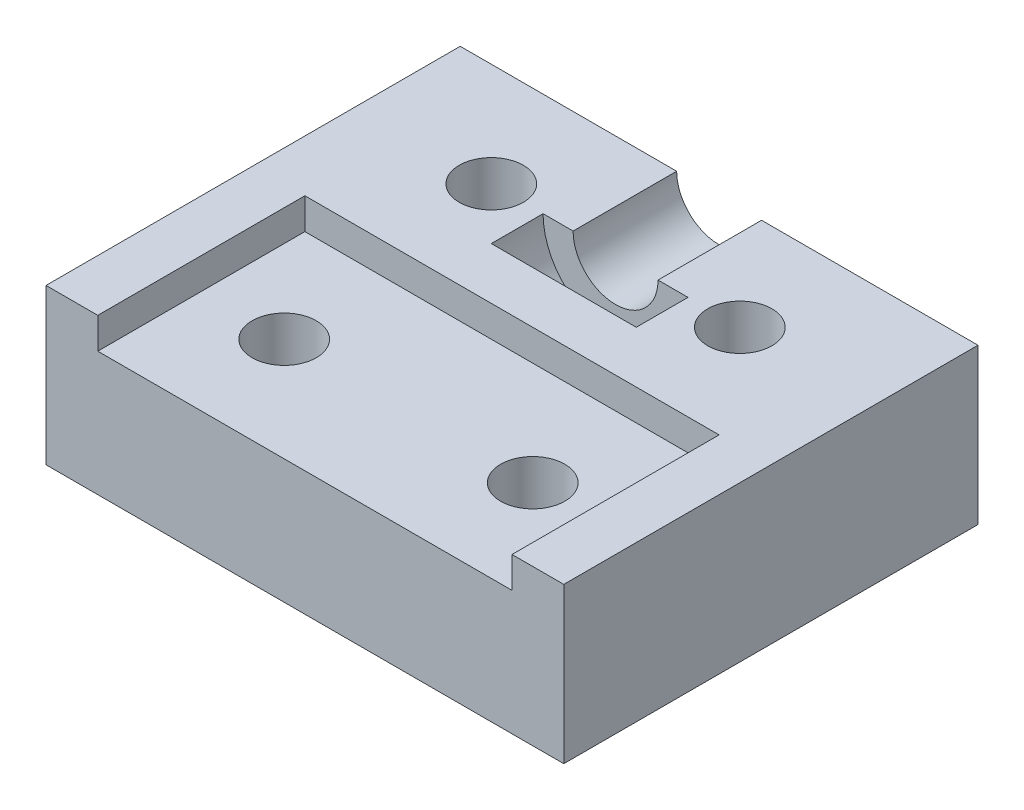
SolidWorks part; units mm, degrees
ref_plane "Front Plane" through (0, 0, 0) normal (0, 0, 1) x (1, 0, 0)
ref_plane "Top Plane" through (0, 0, 0) normal (0, 1, 0) x (1, 0, 0)
ref_plane "Right Plane" through (0, 0, 0) normal (1, 0, 0) x (0, 0, -1)
sketch "Sketch2" plane through (0, 0, 0) normal (0, 1, 0) x (1, 0, 0)
  line L1 (12.5, 10) -> (-12.5, 10)
  line L2 (12.5, 10) -> (12.5, -10)
  line L3 (12.5, -10) -> (-12.5, -10)
  line L4 (-12.5, 10) -> (-12.5, -10)
  line L5 (12.5, 10) -> (-12.5, -10) construction
  line L6 (12.5, -10) -> (-12.5, 10) construction
  point P0 (0, 0)
  dimension "D1" = 20
  dimension "D2" = 25
extrude "Boss-Extrude1" add sketch "Sketch2" against normal blind 7.5
sketch "Sketch3" plane through (0, 0, 10) normal (0, 0, 1) x (1, 0, 0)
  line L1 (10, 1.5) -> (-10, 1.5)
  line L2 (10, 1.5) -> (10, -1.5)
  line L3 (10, -1.5) -> (-10, -1.5)
  line L4 (-10, 1.5) -> (-10, -1.5)
  line L5 (10, 1.5) -> (-10, -1.5) construction
  line L6 (10, -1.5) -> (-10, 1.5) construction
  point P0 (0, 0)
  dimension "D1" = 3
  dimension "D2" = 20
extrude "Cut-Extrude1" cut sketch "Sketch3" against normal blind 10
ref_plane "Plane1" through (0, 0, -5) normal (0, 0, 1) x (1, 0, 0)
sketch "Sketch4" plane through (0, 0, -5) normal (0, 0, 1) x (1, 0, 0)
  circle A0 centre (0, 0) radius 3.5
  dimension "D1" = 7
extrude "Cut-Extrude2" cut sketch "Sketch4" along normal blind 2.5
sketch "Sketch5" plane through (0, 0, -5) normal (0, 0, 1) x (1, 0, 0)
  circle A0 centre (0, 0) radius 2.05
  dimension "D1" = 4.1
extrude "Cut-Extrude3" cut sketch "Sketch5" against normal through all contours A0
sketch "Sketch6" plane through (0, -1.5, 0) normal (0, 1, 0) x (1, 0, 0)
  line L0 (0, 10) -> (0, -10) construction
  line L1 (2.05, 10) -> (-2.05, 10) construction
  line L2 (-10, -10) -> (10, -10) construction
  line L3 (-12.5, -5) -> (12.5, -5) construction
  line L4 (-12.5, 10) -> (-12.5, -10) construction
  line L5 (12.5, -10) -> (12.5, 10) construction
  point P12 (-6, -5)
  point P13 (6, -5)
  dimension "D1" = 5
  dimension "D2" = 12
hole_wizard "Ø3.1 (3.1) Diameter Hole1" positions "Sketch7" profile "Sketch8" hole size "Ø3.1" standard "ISO" end condition through all
sketch "Sketch7" plane through (0, -1.5, 0) normal (0, 1, 0) x (1, 0, 0)
  point P0 (-6, -5)
  point P3 (6, -5)
sketch "Sketch8" plane through (-6, -1.5, 5) normal (1, 0, 0) x (0, 0, 1)
  line L0 (0, 0) -> (0, 6)
  line L1 (0, 6) -> (1.55, 6)
  line L2 (1.55, 6) -> (1.55, 0)
  line L5 (1.55, 0) -> (0, 0)
  line L11 (0, -6.35) -> (0, 107.95) construction
  dimension "Thru Hole Dia." = 3.1
  dimension "Thru Hole Depth" = 6
sketch "Sketch9" plane through (0, 0, 0) normal (0, 1, 0) x (1, 0, 0)
  line L0 (-12.5, 5) -> (12.5, 5) construction
  line L1 (-12.5, 10) -> (-12.5, -10) construction
  line L2 (12.5, -10) -> (12.5, 10) construction
  line L3 (0, 10) -> (0, -10) construction
  line L4 (2.05, 10) -> (-2.05, 10) construction
  line L5 (-10, -10) -> (10, -10) construction
  line L6 (-2.05, 10) -> (-12.5, 10) construction
  point P14 (-6, 5)
  point P15 (6, 5)
  dimension "D1" = 5
  dimension "D2" = 12
hole_wizard "Ø3.1 (3.1) Diameter Hole2" positions "Sketch10" profile "Sketch11" hole size "Ø3.1" standard "ISO" end condition through all
sketch "Sketch10" plane through (0, 0, 0) normal (0, 1, 0) x (1, 0, 0)
  point P0 (-6, 5)
  point P3 (6, 5)
sketch "Sketch11" plane through (-6, 0, -5) normal (1, 0, 0) x (0, 0, 1)
  line L0 (0, 0) -> (0, 7.5)
  line L1 (0, 7.5) -> (1.55, 7.5)
  line L2 (1.55, 7.5) -> (1.55, 0)
  line L5 (1.55, 0) -> (0, 0)
  line L11 (0, -6.35) -> (0, 107.95) construction
  dimension "Thru Hole Dia." = 3.1
  dimension "Thru Hole Depth" = 7.5
